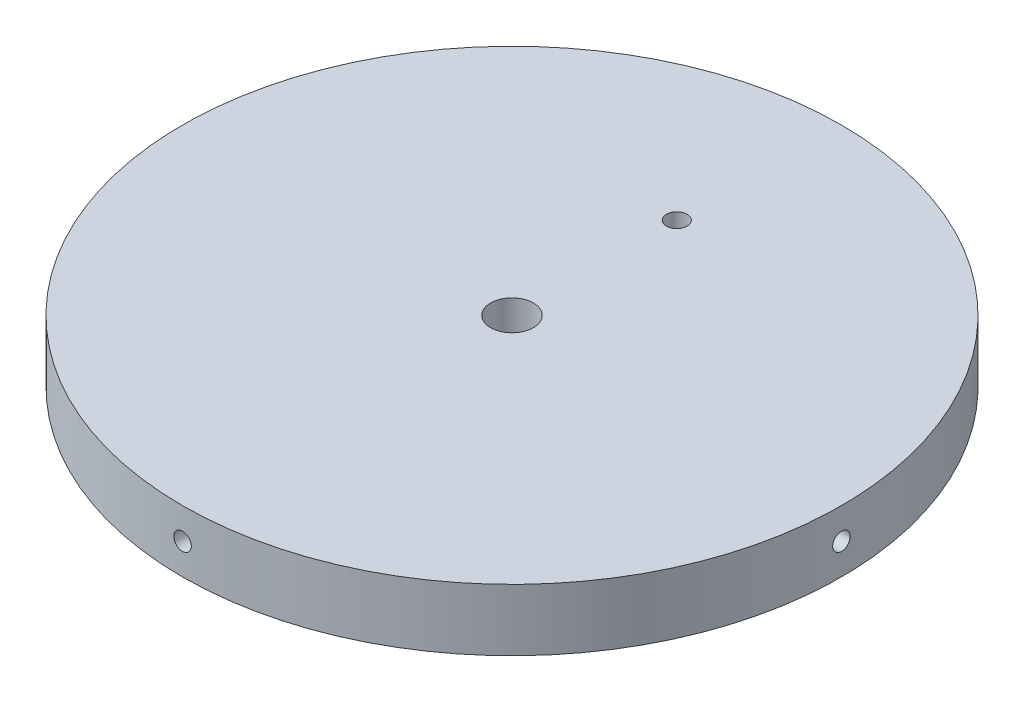
SolidWorks part; units mm, degrees
ref_plane "Front Plane" through (0, 0, 0) normal (0, 0, 1) x (1, 0, 0)
ref_plane "Top Plane" through (0, 0, 0) normal (0, 1, 0) x (1, 0, 0)
ref_plane "Right Plane" through (0, 0, 0) normal (1, 0, 0) x (0, 0, -1)
sketch "Sketch1" plane through (0, 0, 0) normal (0, 1, 0) x (1, 0, 0)
  circle A0 centre (0, 0) radius 50.8
  circle A1 centre (0, 0) radius 3.3
  circle A2 centre (0, 25.4) radius 1.5875
  point P6 (0, 0)
  dimension "D1" = 101.6
  dimension "D2" = 6.6
  dimension "D3" = 3.175
  dimension "D4" = 25.4
extrude "Boss-Extrude1" add sketch "Sketch1" along normal mid plane 9.525
ref_plane "Plane1" through (0, 0, 50.8) normal (0, 0, 1) x (1, 0, 0)
sketch "Sketch2" plane through (0, 0, 50.8) normal (0, 0, 1) x (1, 0, 0)
  circle A0 centre (0, 0) radius 1.3526
  dimension "D1" = 2.7051
extrude "Cut-Extrude1" cut sketch "Sketch2" against normal blind 12.7
sketch "Sketch3" plane through (0, 0, 0) normal (0, 0, 1) x (1, 0, 0)
  line L0 (0, 4.7625) -> (0, -4.7625)
  line L1 (50.8, 4.7625) -> (-50.8, 4.7625) construction
  line L2 (-50.8, -4.7625) -> (50.8, -4.7625) construction
pattern_circular "CirPattern1" count 4 over 360 about axis through (0, 4.7625, 0) along (0, -1, 0) of "Cut-Extrude1"
